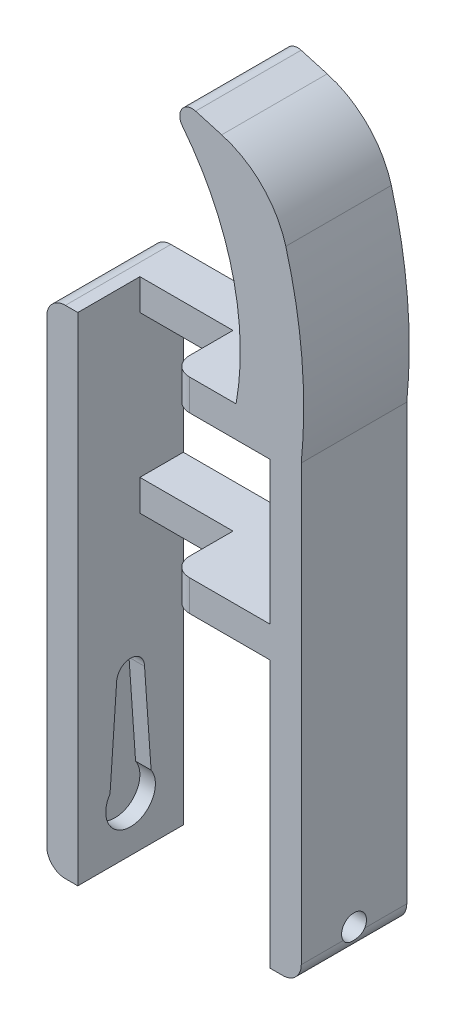
SolidWorks part; units mm, degrees
material "PLA - 20%"
ref_plane "Front Plane" through (0, 0, 0) normal (0, 0, 1) x (1, 0, 0)
ref_plane "Top Plane" through (0, 0, 0) normal (0, 1, 0) x (1, 0, 0)
ref_plane "Right Plane" through (0, 0, 0) normal (1, 0, 0) x (0, 0, -1)
sketch "Sketch1" plane through (0, 0, 0) normal (0, 1, 0) x (1, 0, 0)
  line L1 (0, 0) -> (5, 0)
  line L2 (0, 0) -> (0, -17)
  line L3 (0, -17) -> (5, -17)
  line L4 (5, 0) -> (5, -17)
  line L5 (36, 0) -> (41, 0)
  line L6 (36, 0) -> (36, -17)
  line L7 (36, -17) -> (41, -17)
  line L8 (41, 0) -> (41, -17)
  dimension "D1" = 5
  dimension "D2" = 5
  dimension "D3" = 31
  dimension "D4" = 17
  dimension "D5" = 17
extrude "Boss-Extrude1" add sketch "Sketch1" along normal blind 80
sketch "Sketch2" plane through (5, 0, 0) normal (1, 0, 0) x (0, 0, -1)
  line L0 (-11.8072, 10.25) -> (-10.75, 25.2678)
  line L1 (-11.8072, 10.25) -> (-11.8072, 5.75)
  line L2 (-17, 0) -> (0, 0) construction
  line L3 (-5.1928, 5.75) -> (-5.1928, 10.25)
  line L4 (-5.1928, 10.25) -> (-6.25, 25.2678)
  circle A0 centre (-8.5, 8) radius 4
  arc A1 (-10.75, 25.2678) -> (-6.25, 25.2678) centre (-8.5, 25.2678) cw
  point P6 (-8.5, 0)
  dimension "D1" = 8
  dimension "D3" = 2.25
  dimension "D2" = 4.5
  dimension "D4" = 4.5
  dimension "D5" = 8
extrude "Cut-Extrude1" cut sketch "Sketch2" against normal blind 2.5 contours A1 L0 A0 L4 | L3 A0 L1 | L1 A0 | L3 A0 region at (5, 8, 8.5) region at (5, 18.7534, 8.5) region at (5, 8, 12.0865) region at (5, 8, 4.9135)
sketch "Sketch7" plane through (41, 0, 0) normal (1, 0, 0) x (0, 0, -1)
  line L0 (-17, 80) -> (-17, 0) construction
  line L1 (-17, 4) -> (0, 4)
  line L2 (-17, 4) -> (-17, 0)
  line L3 (-17, 0) -> (0, 0)
  line L4 (0, 4) -> (0, 0)
  dimension "D1" = 4
extrude "Cut-Extrude4" cut sketch "Sketch7" against normal up to next (5 mm away)
sketch "Sketch8" plane through (41, 0, 0) normal (1, 0, 0) x (0, 0, -1)
  circle A0 centre (-8.5, 8) radius 2
  dimension "D1" = 4
extrude "Cut-Extrude5" cut sketch "Sketch8" against normal up to next (5 mm away)
sketch "Sketch9" plane through (5, 0, 0) normal (1, 0, 0) x (0, 0, -1)
  line L1 (-7, 80) -> (0, 80)
  line L2 (-7, 80) -> (-7, 75)
  line L3 (-7, 75) -> (0, 75)
  line L4 (0, 80) -> (0, 75)
  line L5 (-17, 80) -> (-17, 0) construction
  line L6 (0, 80) -> (0, 0) construction
  line L7 (-17, 80) -> (0, 80) construction
  line L9 (-7, 52) -> (0, 52)
  line L10 (-7, 52) -> (-7, 47)
  line L11 (-7, 47) -> (0, 47)
  line L12 (0, 52) -> (0, 47)
  dimension "D1" = 10
  dimension "D2" = 5
  dimension "D3" = 23
  dimension "D4" = 5
extrude "Boss-Extrude3" add sketch "Sketch9" along normal up to next
sketch "Sketch10" plane through (36, 0, 0) normal (-1, 0, 0) x (0, 0, 1)
  line L0 (17, 80) -> (17, 4) construction
  line L1 (17, 80) -> (7, 80)
  line L2 (17, 80) -> (17, 75)
  line L3 (17, 75) -> (7, 75)
  line L4 (7, 80) -> (7, 75)
  line L5 (7, 47) -> (17, 47)
  line L6 (7, 47) -> (7, 52)
  line L7 (7, 52) -> (17, 52)
  line L8 (17, 47) -> (17, 52)
extrude "Boss-Extrude4" add sketch "Sketch10" along normal blind 16
fillet "Fillet3" radius 3 6 edges at (41, 4, 8.5) (0, 0, 8.5) (41, 80, 8.5) (0, 80, 8.5) (20, 77.5, 17) (20, 49.5, 17)
sketch "Sketch12" plane through (0, 0, 17) normal (0, 0, 1) x (1, 0, 0)
  line L0 (23, 80) -> (38, 80) construction
  line L1 (17.0712, 119.5582) -> (35.7099, 114.2329)
  line L2 (30.5, 80) -> (41, 77)
  arc A0 (17.0712, 119.5582) -> (30.5, 80) centre (-12.0394, 87.6176) cw
  arc A1 (35.7099, 114.2329) -> (41, 77) centre (-37.2056, 84.8806) cw
  point P0 (23, 80)
  point P1 (17.0712, 119.5582)
  dimension "D1" = 40
extrude "Boss-Extrude5" add sketch "Sketch12" against normal through all
fillet "Fillet4" radius 2 1 edges at (17.0712, 119.5582, 8.5)
fillet "Fillet5" radius 15 1 edges at (35.7099, 114.2329, 8.5)
